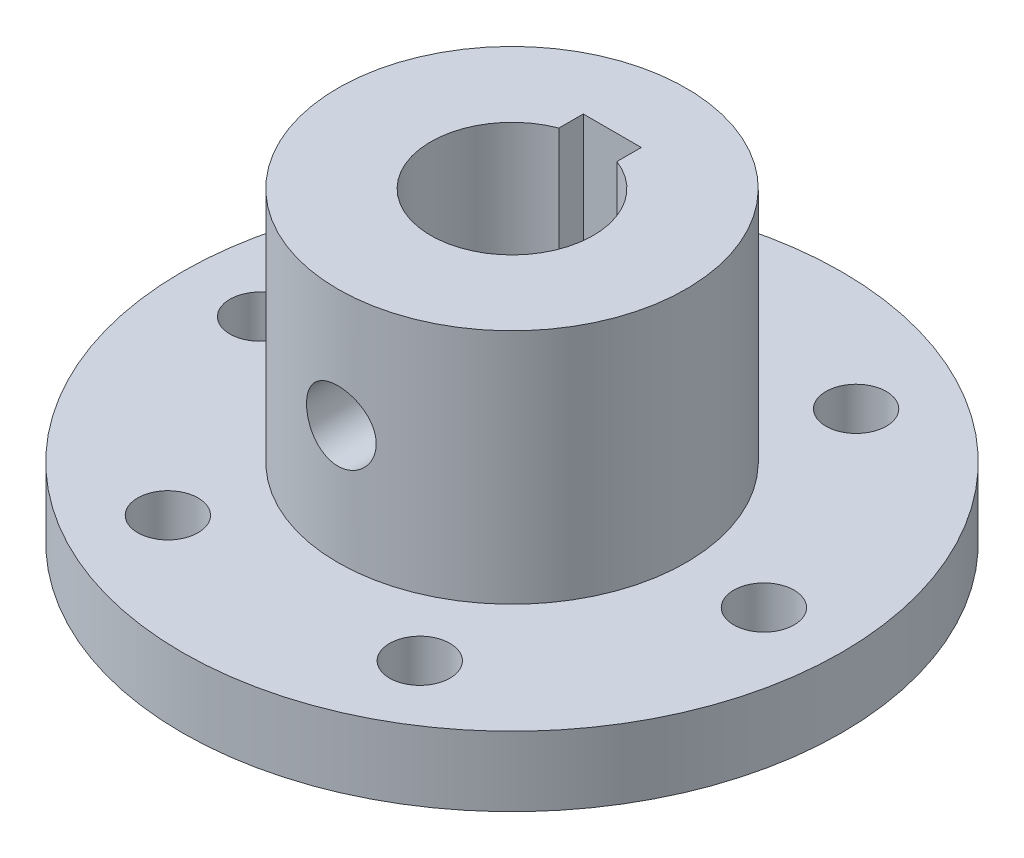
SolidWorks part; units mm, degrees
ref_plane "Front Plane" through (0, 0, 0) normal (0, 0, 1) x (1, 0, 0)
ref_plane "Top Plane" through (0, 0, 0) normal (0, 1, 0) x (1, 0, 0)
ref_plane "Right Plane" through (0, 0, 0) normal (1, 0, 0) x (0, 0, -1)
sketch "Sketch1" plane through (0, 0, 0) normal (0, 1, 0) x (1, 0, 0)
  circle A0 centre (0, 0) radius 28.4
  dimension "D1" = 56.8
extrude "Boss-Extrude1" add sketch "Sketch1" along normal blind 6
sketch "Sketch2" plane through (0, 6, 0) normal (0, 1, 0) x (1, 0, 0)
  circle A0 centre (0, 0) radius 15
  dimension "D1" = 30
extrude "Boss-Extrude2" add sketch "Sketch2" along normal blind 20.4
sketch "Sketch3" plane through (0, 26.4, 0) normal (0, 1, 0) x (1, 0, 0)
  line L1 (-2.5, 8.6383) -> (2.5, 8.6383)
  line L2 (-2.5, 8.6383) -> (-2.5, 6.5383)
  line L4 (2.5, 8.6383) -> (2.5, 6.5383)
  line L5 (-2.5, 8.6383) -> (2.5, 6.5383) construction
  line L6 (-2.5, 6.5383) -> (2.5, 8.6383) construction
  arc A0 (-2.5, 6.5383) -> (2.5, 6.5383) centre (0, 0) ccw
  point P7 (0, 7.5883)
  point P8 (0, 0)
  point P9 (0, 0)
  point P10 (0, 8.6383)
  dimension "D1" = 14
  dimension "D2" = 5
  dimension "D3" = 2.1
extrude "Cut-Extrude1" cut sketch "Sketch3" against normal through all
sketch "Sketch4" plane through (0, 0, 0) normal (0, 0, 1) x (1, 0, 0)
  line L0 (7, 26.4) -> (-7, 26.4) construction
  line L1 (0, 0) -> (0, 16.2) construction
  circle A0 centre (0, 16.2) radius 3
  dimension "D1" = 6
  dimension "D2" = 10.2
extrude "Cut-Extrude2" cut sketch "Sketch4" along normal through all
sketch "Sketch5" plane through (0, 6, 0) normal (0, 1, 0) x (1, 0, 0)
  line L0 (-21.7, 0) -> (-28.4, 0) construction
  line L1 (-21.7, 0) -> (-15, 0) construction
  line L2 (-21.7, 0) -> (-21.7, 18.3213) construction
  line L3 (-21.7, 0) -> (-21.7, -18.3213) construction
  circle A0 centre (-21.7, 0) radius 2.6
  circle A1 centre (0, 0) radius 28.4 construction
  circle A2 centre (0, 0) radius 15 construction
  dimension "D1" = 5.2
extrude "Cut-Extrude3" cut sketch "Sketch5" against normal through all
pattern_circular "CirPattern1" count 6 over 360 about axis through (0, 6, 0) along (0, 1, 0) of "Cut-Extrude3"
